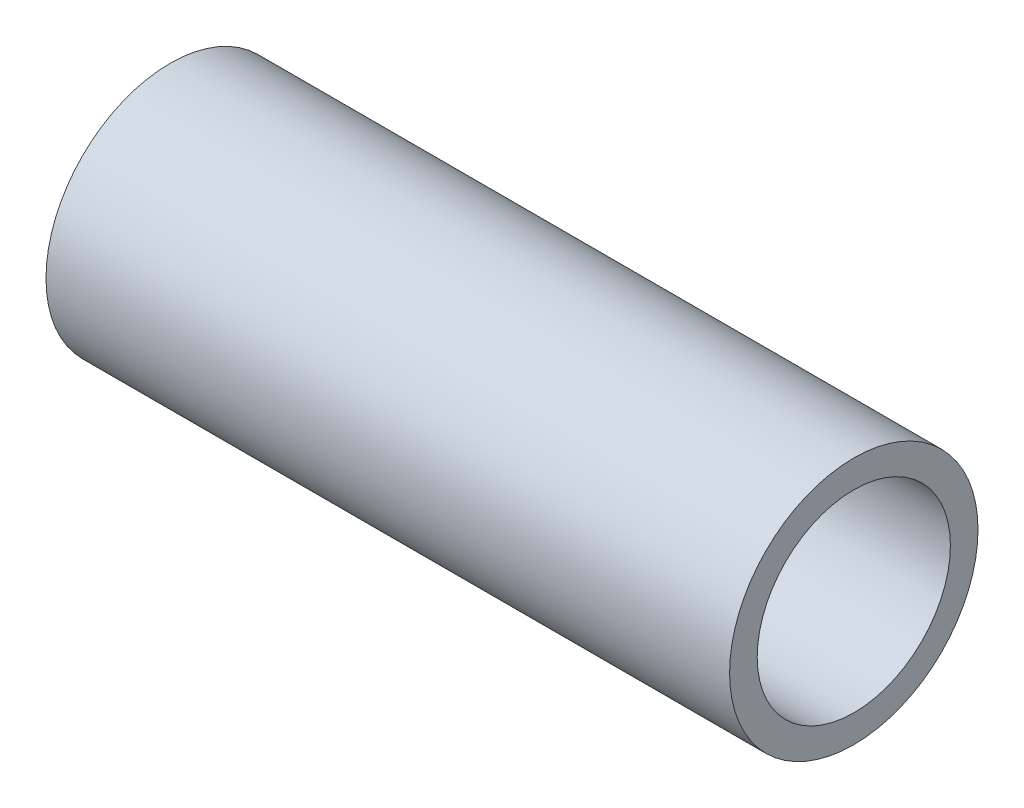
SolidWorks part; units mm, degrees
ref_plane "Front Plane" through (0, 0, 0) normal (0, 0, 1) x (1, 0, 0)
ref_plane "Top Plane" through (0, 0, 0) normal (0, 1, 0) x (1, 0, 0)
ref_plane "Right Plane" through (0, 0, 0) normal (1, 0, 0) x (0, 0, -1)
sketch "Sketch1" plane through (0, 0, 0) normal (0, 0, 1) x (1, 0, 0)
  line L0 (0, 0) -> (43.7471, 0) construction
  line L1 (0, 6) -> (0, 14.2875)
  line L2 (0, 14.2875) -> (78.6384, 14.2875)
  line L3 (78.6384, 14.2875) -> (78.6384, 11.1125)
  line L4 (78.6384, 11.1125) -> (53.2384, 11.1125)
  line L6 (53.2384, 11.1125) -> (53.2384, 12.7)
  line L7 (53.2384, 12.7) -> (15.875, 12.7)
  line L8 (15.875, 12.7) -> (15.875, 6)
  line L9 (15.875, 6) -> (0, 6)
  dimension "D1" = 6
  dimension "D2" = 14.2875
  dimension "D3" = 15.875
  dimension "D4" = 78.6384
  dimension "D5" = 25.4
  dimension "D6" = 3.175
  dimension "D7" = 1.5875
revolve "Revolve1" add sketch "Sketch1" angle 360 about L0
thread "Thread1" pitch 1.5 method cut profile "Thread Profile1" start angle 0, offset 0, length 19.05, pitch 1.5, diameter 12
ref_plane "Plane1" through (0, 0, -6) normal (0, -1, 0) x (0, 0, -1)
sketch "Thread Profile1" plane through (0, 0, -6) normal (0, -1, 0) x (0, 0, -1)
  line L0 (0, 0) -> (0, 1.5) construction
  line L1 (0, 0) -> (0.8119, 0.4687)
  line L2 (0.8119, 0.4687) -> (0.8119, 0.6562)
  line L3 (0.8119, 0.6562) -> (0, 1.125)
  line L4 (0.8119, 0.5625) -> (0, 0.5625) construction
  line L11 (0, 0) -> (0, 1.125)
  point P2 (0, 0)
  dimension "Pitch" = 1.5
  dimension "Profile_Angle" = 60
  dimension "Profile_Land" = 0.1875
  dimension "Profile_Height" = 0.8119
